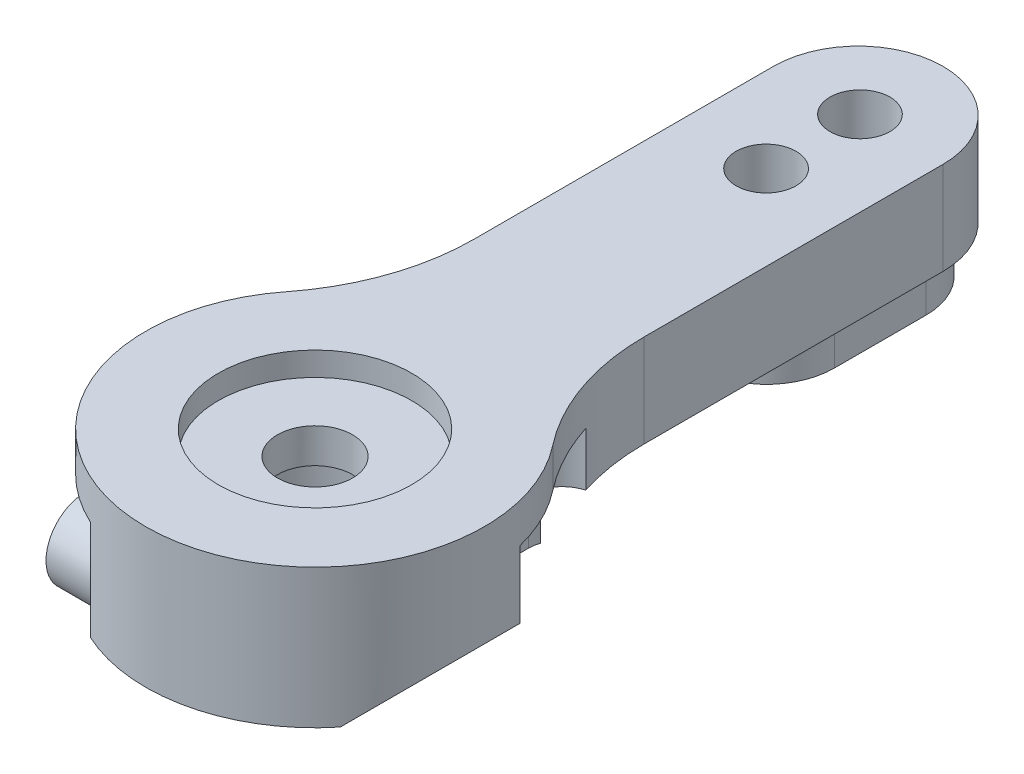
SolidWorks part; units mm, degrees
ref_plane "Front Plane" through (0, 0, 0) normal (0, 0, 1) x (1, 0, 0)
ref_plane "Top Plane" through (0, 0, 0) normal (0, 1, 0) x (1, 0, 0)
ref_plane "Right Plane" through (0, 0, 0) normal (1, 0, 0) x (0, 0, -1)
sketch "Sketch1" plane through (0, 0, 0) normal (0, 1, 0) x (1, 0, 0)
  line L0 (0, 24.015) -> (0, 0) construction
  line L1 (3.75, 24.015) -> (3.75, 0)
  line L2 (-3.75, 24.015) -> (-3.75, 0)
  line L3 (0, 24.015) -> (0, 19.955) construction
  line L4 (3, 24.015) -> (3, 19.955)
  line L5 (-3, 24.015) -> (-3, 19.955)
  circle A0 centre (0, 0) radius 7.485
  arc A1 (3.75, 24.015) -> (-3.75, 24.015) centre (0, 24.015) ccw
  arc A2 (-3.75, 0) -> (3.75, 0) centre (0, 0) ccw
  arc A3 (3, 24.015) -> (-3, 24.015) centre (0, 24.015) ccw
  arc A4 (-3, 19.955) -> (3, 19.955) centre (0, 19.955) ccw
  point P3 (0, 12.0075)
  point P11 (0, 21.985)
  dimension "D2" = 14.97
  dimension "D1" = 7.5
  dimension "D3" = 24.015
  dimension "D4" = 6
  dimension "D5" = 4.06
extrude "Boss-Extrude1" add sketch "Sketch1" along normal blind 2.05 contours A2 L2 A0 L1 | L5 A4 L4 A3 | L2 A2 L1 A0 region at (6.307, 0, -3.6365) region at (0, 0, -2.0765) region at (0, 0, -21.985)
extrude "Boss-Extrude2" add sketch "Sketch1<3>" along normal blind 4.1 from surface contours A2 L2 A0 L1 | L2 A2 L1 A0 | L1 A1 L2 A0 A4 L5 A3 L4 | L5 A4 L4 A3 region at (0, 0, -14.3795) region at (6.307, 0, -3.6365) region at (0, 0, -2.0765) region at (0, 0, -21.985) starting at face at (0, 2.05, -21.985)
sketch "Sketch1<3>" plane through (0, 0, 0) normal (0, 1, 0) x (1, 0, 0) same geometry as "Sketch1"
fillet "Fillet1" radius 10 2 edges at (-3.75, 4.1, -6.4779) (3.75, 4.1, -6.4779)
sketch "Sketch2" plane through (0, 6.15, 0) normal (0, 1, 0) x (1, 0, 0)
  circle A0 centre (0, 0) radius 1.66
  circle A1 centre (0, 0) radius 4.275
  dimension "D1" = 3.32
  dimension "D2" = 8.55
extrude "Cut-Extrude1" cut sketch "Sketch2" against normal through all contours A0 region at (0, 6.15, 0)
extrude "Cut-Extrude2" cut sketch "Sketch2<3>" against normal blind 1.05 contours A1 A0 region at (-4.1541, 6.15, 0)
sketch "Sketch2<3>" plane through (0, 6.15, 0) normal (0, 1, 0) x (1, 0, 0) same geometry as "Sketch2"
sketch "Sketch3" plane through (0, 0, 0) normal (0, -1, 0) x (-1, 0, 0)
  circle A0 centre (0, 19.94) radius 1.325
  circle A1 centre (0, 24.09) radius 1.325
  circle A2 centre (0, 0) radius 7.485 construction
  dimension "D1" = 2.65
  dimension "D2" = 4.15
  dimension "D3" = 24.09
extrude "Cut-Extrude3" cut sketch "Sketch3" against normal through all
sketch "Sketch4" plane through (0, 0, 0) normal (0, 0, 1) x (1, 0, 0)
  line L0 (5.8233, 0) -> (7.485, 1.6617)
  line L1 (-7.485, 0) -> (7.485, 0) construction
  line L2 (7.485, 0) -> (7.485, 6.15) construction
  dimension "D1" = 2.35
  dimension "D2" = 45
extrude "Cut-Extrude4" cut sketch "Sketch4" against normal through all and the other way through all flip side to cut
mirror "Mirror1" about plane through (0, 0, 0) normal (1, 0, 0) of "Cut-Extrude4"
sketch "Sketch5" plane through (0, 0, 0) normal (0, -1, 0) x (1, 0, 0)
  line L1 (21.7205, -1.7974) -> (4.635, -1.7974)
  line L2 (21.7205, -1.7974) -> (21.7205, -7.7974)
  line L3 (21.7205, -7.7974) -> (4.635, -7.7974)
  line L4 (3.135, -3.2974) -> (3.135, -6.2974)
  line L10 (-4.635, 1.7974) -> (-13.9063, 1.7974)
  line L11 (-3.135, 3.2974) -> (-3.135, 10.5078)
  line L12 (-3.135, 10.5078) -> (-13.9063, 10.5078)
  line L13 (-13.9063, 1.7974) -> (-13.9063, 10.5078)
  arc A0 (4.635, -7.7974) -> (3.135, -6.2974) centre (4.635, -6.2974) cw
  arc A1 (4.635, -1.7974) -> (3.135, -3.2974) centre (4.635, -3.2974) ccw
  arc A4 (-4.635, 1.7974) -> (-3.135, 3.2974) centre (-4.635, 3.2974) ccw
  dimension "D1" = 1.5
  dimension "D5" = 1.5
  dimension "D2" = 3
  dimension "D3" = 3.135
  dimension "D4" = 6.5
  dimension "D6" = 6.5
  dimension "D7" = 3.135
extrude "Cut-Extrude5" cut sketch "Sketch5" against normal blind 4.42
sketch "Sketch6" plane through (0, 0, 0) normal (0, -1, 0) x (1, 0, 0)
  circle A0 centre (0, 0) radius 3
  dimension "D1" = 6
extrude "Cut-Extrude6" cut sketch "Sketch6" against normal blind 3.57
sketch "Sketch7" plane through (-3.135, 0, 0) normal (-1, 0, 0) x (0, 0, 1)
  line L1 (1.7974, 4.42) -> (1.7974, 0) construction
  line L2 (3.2974, 4.42) -> (6.7968, 4.42) construction
  circle A0 centre (4.9974, 1.92) radius 1.76
  dimension "D1" = 3.52
  dimension "D2" = 3.2
  dimension "D3" = 2.5
extrude "Boss-Extrude3" add sketch "Sketch7" along normal blind 2
move or copy body "Body-Move/Copy1" [suppressed] bodies to move or copy 111
equation "\"D3@Sketch1\"=35.25-\"D1@Sketch1\"/2-\"D2@Sketch1\"/2"
equation "\"D5@Sketch1\"=10.06-\"D4@Sketch1\""
equation "\"D2@Sketch3\"=1.5+\"D1@Sketch3\""
equation "\"D3@Sketch3\"=30.25+\"D1@Sketch3\"/2-14.97/2"
equation "\"D3@Sketch5\"=2.58+1.11/2"
equation "\"D6@Sketch5\"=\"D4@Sketch5\""
equation "\"D7@Sketch5\"=\"D3@Sketch5\""
